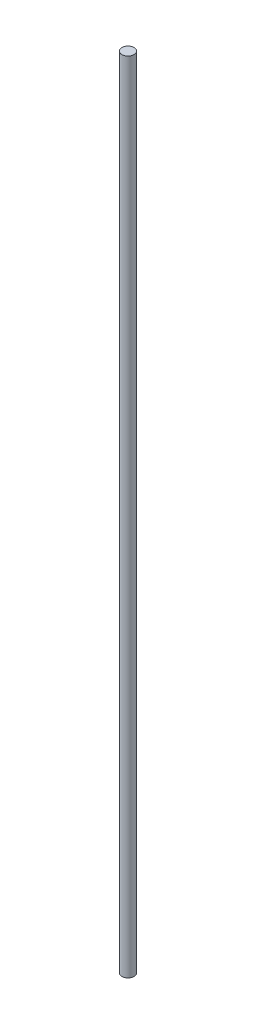
SolidWorks part; units mm, degrees
material "AISI 304"
ref_plane "Front" through (0, 0, 0) normal (0, 0, 1) x (1, 0, 0)
ref_plane "Top" through (0, 0, 0) normal (0, 1, 0) x (1, 0, 0)
ref_plane "Right" through (0, 0, 0) normal (1, 0, 0) x (0, 0, -1)
ref_axis "side-side" through (80.9, 0, 0) along (-1, 0, 0)
ref_axis "up-down" through (0, 50, 0) along (0, -1, 0)
ref_axis "front-back" through (0, 0, -80.9) along (0, 0, 1)
sketch "Sketch1" plane through (0, 0, 0) normal (0, 1, 0) x (1, 0, 0)
  circle A0 centre (0, 0) radius 2.3812
  dimension "D1" = 4.7625
extrude "Boss-Extrude1" add sketch "Sketch1" along normal blind 309.88
